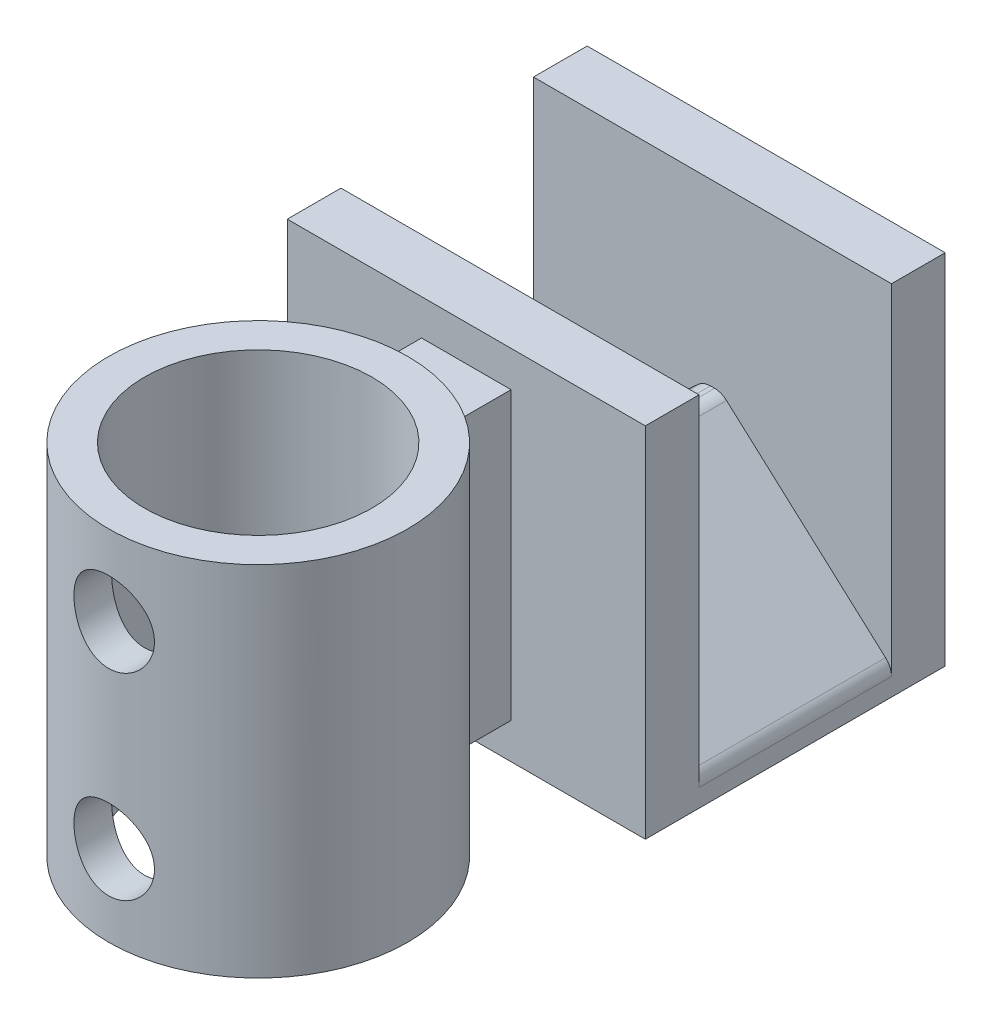
SolidWorks part; units mm, degrees
ref_plane "Front Plane" through (0, 0, 0) normal (0, 0, 1) x (1, 0, 0)
ref_plane "Top Plane" through (0, 0, 0) normal (0, 1, 0) x (1, 0, 0)
ref_plane "Right Plane" through (0, 0, 0) normal (1, 0, 0) x (0, 0, -1)
sketch "Sketch2" plane through (0, 0, 0) normal (0, 0, 1) x (1, 0, 0)
  line L1 (-10, -5) -> (10, -5)
  line L2 (-10, -5) -> (-10, 5)
  line L3 (-10, 5) -> (10, 5)
  line L4 (10, -5) -> (10, 5)
  line L5 (-10, -5) -> (10, 5) construction
  line L6 (-10, 5) -> (10, -5) construction
  point P0 (0, 0)
  dimension "D1" = 10
  dimension "D2" = 20
extrude "Boss-Extrude1" add sketch "Sketch2" along normal mid plane 10.75
chamfer "Chamfer1" distance 9.5 angle 42 2 edges at (10, 5, 0) (-10, 5, 0) first distance on face at (0, 5, 0)
fillet "Fillet3" radius 1 4 edges at (-10, -3.5538, 0) (10, -3.5538, 0) (0.5, 5, 0) (-0.5, 5, 0)
sketch "Sketch3" plane through (0, 0, 5.375) normal (0, 0, 1) x (1, 0, 0)
  line L0 (-10, -5) -> (10, -5) construction
  line L1 (-10, 15) -> (10, 15)
  line L2 (-10, 15) -> (-10, -5)
  line L3 (-10, -5) -> (10, -5)
  line L4 (10, 15) -> (10, -5)
  line L5 (-10, 15) -> (10, -5) construction
  line L6 (-10, -5) -> (10, 15) construction
  point P0 (0, 5)
  dimension "D1" = 20
  dimension "D2" = 20
extrude "Boss-Extrude2" add sketch "Sketch3" along normal blind 3
mirror "Mirror1" about plane through (0, 0, 0) normal (0, 0, 1) of "Boss-Extrude2"
sketch "Sketch6" plane through (0, 0, 0) normal (0, 1, 0) x (1, 0, 0)
  circle A0 centre (0, -20) radius 6.35
  circle A1 centre (0, -20) radius 8.35
  dimension "D1" = 12.7
  dimension "D2" = 2
  dimension "D3" = 20
extrude "Boss-Extrude3" add sketch "Sketch6" along normal up to surface and the other way up to surface separate body up to face at (0, 15, 6.875) other way up to face at (0, -5, 0)
sketch "Sketch5" plane through (0, 0, 8.375) normal (0, 0, 1) x (1, 0, 0)
  line L0 (-10, -5) -> (10, -5) construction
  line L1 (-2.5, 13) -> (2.5, 13)
  line L2 (-2.5, 13) -> (-2.5, -3)
  line L3 (-2.5, -3) -> (2.5, -3)
  line L4 (2.5, 13) -> (2.5, -3)
  line L5 (-2.5, 13) -> (2.5, -3) construction
  line L6 (-2.5, -3) -> (2.5, 13) construction
  line L7 (10, 15) -> (-10, 15) construction
  point P0 (0, 5)
  dimension "D1" = 2
  dimension "D2" = 2
  dimension "D3" = 5
extrude "Boss-Extrude4" add sketch "Sketch5" along normal up to surface (3.658 mm away) up to face at (0, 15, 11.65)
ref_plane "Plane1" through (0, 0, 20) normal (0, 0, 1) x (1, 0, 0)
sketch "Sketch7" plane through (0, 0, 20) normal (0, 0, 1) x (1, 0, 0)
  line L0 (-8.35, -5) -> (8.35, -5) construction
  line L1 (6.35, 15) -> (-6.35, 15) construction
  circle A0 centre (0, 10.5) radius 2.25
  circle A1 centre (0, -0.5) radius 2.25
  dimension "D1" = 4.5
  dimension "D2" = 4.5
  dimension "D3" = 4.5
  dimension "D4" = 4.5
extrude "Cut-Extrude1" cut sketch "Sketch7" along normal up to surface (8.0412 mm away) up to face at (0, 15, 11.65)
